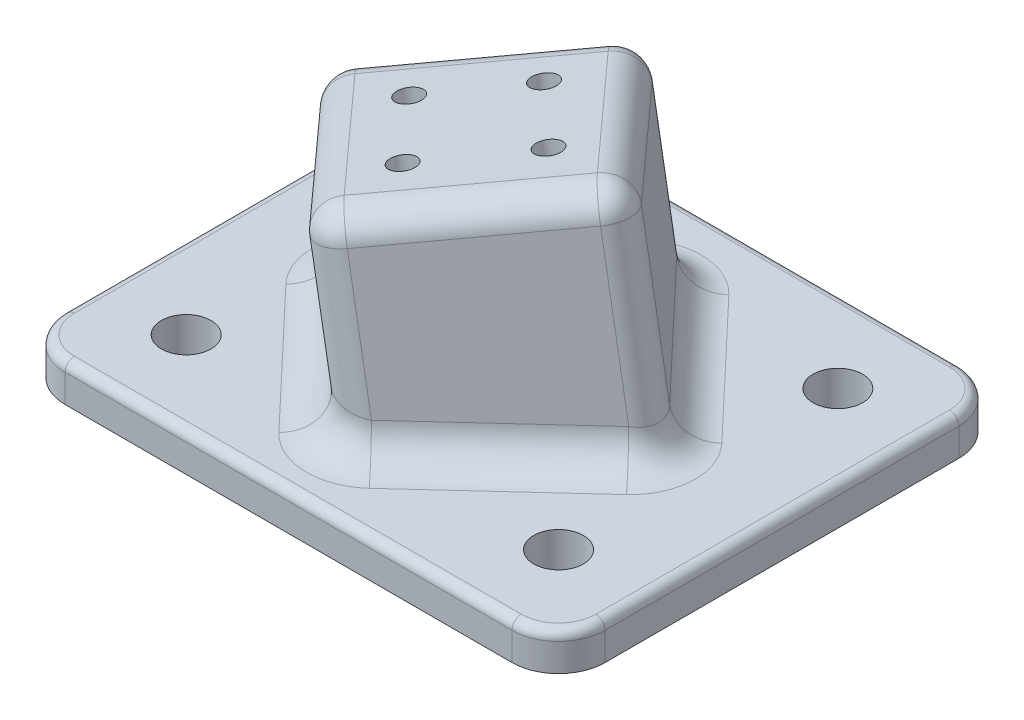
SolidWorks part; units mm, degrees
ref_plane "Front Plane" through (0, 0, 0) normal (0, 0, 1) x (1, 0, 0)
ref_plane "Top Plane" through (0, 0, 0) normal (0, 1, 0) x (1, 0, 0)
ref_plane "Right Plane" through (0, 0, 0) normal (1, 0, 0) x (0, 0, -1)
sketch "Sketch1" plane through (0, 0, 0) normal (0, 1, 0) x (1, 0, 0)
  line L1 (0, 0) -> (63.5, 0)
  line L2 (0, 0) -> (0, -50.8)
  line L3 (0, -50.8) -> (63.5, -50.8)
  line L4 (63.5, 0) -> (63.5, -50.8)
  dimension "D1" = 63.5
  dimension "D2" = 50.8
extrude "Boss-Extrude1" add sketch "Sketch1" along normal blind 5.08
sketch "Sketch2" plane through (0, 5.08, 0) normal (0, 1, 0) x (1, 0, 0)
  line L1 (0, 0) -> (0, -50.8) construction
  line L2 (63.5, 0) -> (0, 0) construction
  point P0 (6.35, -6.35)
  point P1 (57.15, -6.35)
  point P2 (57.15, -44.45)
  point P3 (6.35, -44.45)
  dimension "D1" = 50.8
  dimension "D2" = 38.1
  dimension "D3" = 50.8
  dimension "D4" = 38.1
  dimension "D5" = 6.35
  dimension "D6" = 6.35
ref_plane "Plane2" through (1.9148, -10.8591, 0) normal (-0.1736, 0.9848, 0) x (0, 0, -1)
sketch "Sketch5" plane through (0, 0, 0) normal (0, -1, 0) x (1, 0, 0)
  line L0 (0, 0) -> (0, 50.8) construction
  line L1 (0, 50.8) -> (63.5, 50.8)
  line L2 (0, 50.8) -> (0, 0)
  line L3 (0, 0) -> (63.5, 0)
  line L4 (63.5, 50.8) -> (63.5, 0)
  line L5 (63.5, 0) -> (0, 0) construction
  dimension "D1" = 50.8
  dimension "D2" = 63.5
  dimension "D3" = 0
  dimension "D4" = 0
hole_wizard "1/4 Clearance Hole1" positions "3DSketch2" profile "Sketch8" hole size "1/4" standard "ANSI Inch" end condition up to next
sketch3d "3DSketch2"
  point P0 (6.35, 5.08, 6.35)
  point P3 (6.35, 5.08, 44.45)
  point P6 (57.15, 5.08, 44.45)
  point P9 (57.15, 5.08, 6.35)
sketch "Sketch8" plane through (6.35, 5.08, 6.35) normal (1, 0, 0) x (0, 0, 1)
  line L0 (0, 0) -> (0, 5.08)
  line L1 (0, 5.08) -> (3.3782, 5.08)
  line L2 (3.3782, 5.08) -> (3.3782, 0)
  line L5 (3.3782, 0) -> (0, 0)
  line L11 (0, -6.35) -> (0, 107.95) construction
  dimension "Thru Hole Dia." = 6.7564
  dimension "Thru Hole Depth" = 5.08
sketch "Sketch13" plane through (0, 5.08, 0) normal (0, 1, 0) x (1, 0, 0)
  line L0 (0, 0) -> (63.5, 0)
  line L1 (63.5, 0) -> (63.5, -50.8)
  line L2 (63.5, -50.8) -> (0, -50.8)
  line L3 (0, 0) -> (0, -50.8) construction
  line L4 (0, -50.8) -> (63.5, -50.8) construction
  line L5 (0, -50.8) -> (0, 0)
  line L6 (-5.08, 5.08) -> (68.58, 5.08)
  line L7 (68.58, 5.08) -> (68.58, -55.88)
  line L8 (68.58, -55.88) -> (-5.08, -55.88)
  line L9 (-5.08, -55.88) -> (-5.08, 5.08)
  dimension "D1" = 73.66
  dimension "D2" = 60.96
  dimension "D3" = 5.08
  dimension "D4" = 5.08
extrude "Boss-Extrude3" add sketch "Sketch13" against normal blind 5.08
fillet "Fillet4" radius 1.27 4 edges at (68.58, 5.08, 25.4) (31.75, 5.08, -5.08) (31.75, 5.08, 55.88) (-5.08, 5.08, 25.4)
sketch "Sketch14" plane through (1.9148, -10.8591, 0) normal (-0.1736, 0.9848, 0) x (0, 0, -1)
  line L0 (-25.4, -9.9293) -> (-48.992, -31.9292)
  line L1 (-48.992, -31.9292) -> (-26.9921, -55.5213)
  line L2 (-26.9921, -55.5213) -> (-3.4001, -33.5213)
  line L3 (-3.4001, -33.5213) -> (-25.4, -9.9293)
  line L4 (5.08, 5.0028) -> (-55.88, 5.0028) construction
  line L6 (-55.88, -68.1997) -> (-55.88, 4.3412) construction
  point P6 (-25.4, 5.0028)
  point P11 (-55.88, -31.9292)
  dimension "D1" = 90
  dimension "D2" = 90
  dimension "D3" = 32.258
  dimension "D4" = 32.258
extrude "Boss-Extrude4" add sketch "Sketch14" along normal blind 37.338
sketch "Sketch16" plane through (0, 0, 0) normal (0, -1, 0) x (1, 0, 0)
  line L1 (0, 50.8) -> (63.5, 50.8)
  line L2 (0, 50.8) -> (0, 0)
  line L3 (0, 0) -> (63.5, 0)
  line L4 (63.5, 50.8) -> (63.5, 0)
sketch "Sketch17" plane through (1.9148, -10.8591, 0) normal (0.1736, -0.9848, 0) x (0.9848, 0.1736, 0)
  line L0 (13.5193, 25.5254) -> (33.396, 6.99)
  line L1 (33.396, 6.99) -> (51.9313, 26.8667)
  line L2 (51.9313, 26.8667) -> (32.0546, 45.4021)
  line L3 (32.0546, 45.4021) -> (13.5193, 25.5254)
  line L5 (33.5213, 3.4001) -> (9.9293, 25.4) construction
  line L6 (9.9293, 25.4) -> (31.9292, 48.992) construction
  line L7 (55.5213, 26.9921) -> (31.9292, 48.992) construction
  line L8 (33.5213, 3.4001) -> (55.5213, 26.9921) construction
  dimension "D1" = 2.54
  dimension "D2" = 2.54
  dimension "D3" = 2.54
  dimension "D4" = 2.54
extrude "Cut-Extrude2" cut sketch "Sketch17" against normal blind 32.258
extrude "Cut-Extrude1" cut sketch "Sketch5" along normal up to next contours L2 L3 L4 L1
sketch "Sketch18" plane through (-4.5689, 25.9116, 0) normal (-0.1736, 0.9848, 0) x (0.9848, 0.1736, 0)
  line L0 (33.5213, -3.4001) -> (55.5213, -26.9921) construction
  line L1 (55.5213, -26.9921) -> (31.9292, -48.992) construction
  point P0 (42.3701, -25.8234)
  point P1 (32.7253, -26.196)
  point P2 (23.0733, -25.8288)
  point P3 (32.3273, -16.544)
  point P4 (32.3273, -35.848)
  dimension "D1" = 16.129
  dimension "D2" = 16.129
  dimension "D3" = 9.652
  dimension "D4" = 9.652
  dimension "D5" = 9.652
  dimension "D6" = 9.652
hole_wizard "M3 Clearance Hole1" positions "3DSketch3" profile "Sketch19" hole size "M3" standard "ANSI Metric" end condition through all
sketch3d "3DSketch3"
  point P0 (27.2672, 31.5252, 16.544)
  point P3 (37.1575, 33.2691, 25.8234)
  point P6 (27.2672, 31.5252, 35.848)
  point P9 (18.1538, 29.9182, 25.8288)
sketch "Sketch19" plane through (27.2672, 31.5252, 16.544) normal (0, 0, 1) x (-0.9848, -0.1736, 0)
  line L0 (0, 0) -> (0, 38.2201)
  line L1 (0, 38.2201) -> (1.7, 38.2201)
  line L2 (1.7, 38.2201) -> (1.7, 0)
  line L5 (1.7, 0) -> (0, 0)
  line L11 (0, -6.35) -> (0, 107.95) construction
  dimension "Thru Hole Dia." = 3.4
  dimension "Thru Hole Depth" = 38.2201
fillet "Fillet5" radius 3.81 8 edges at (39.276, 33.6427, 15.1961) (30.7929, 18.4063, 3.4001) (16.8264, 29.6842, 14.4) (7.1982, 16.3579, 25.4) (16.0424, 29.5459, 37.196) (29.2007, 18.268, 48.992) (38.492, 33.5044, 37.9921) (52.7954, 20.3164, 26.9921)
fillet "Fillet6" radius 6.35 8 edges at (68.208, 4.708, -4.708) (-4.708, 4.708, -4.708) (-4.708, 4.708, 55.508) (68.208, 4.708, 55.508) (68.58, 1.905, 55.88) (-5.08, 1.905, 55.88) (-5.08, 1.905, -5.08) (68.58, 1.905, -5.08)
fillet "Fillet7" radius 5.08 8 edges at (44.3124, 5.08, 15.1961) (21.1647, 5.08, 14.4) (20.3564, 5.08, 37.196) (43.504, 5.08, 37.9921) (10.7883, 5.08, 25.4551) (31.582, 5.08, 47.4148) (33.0868, 5.08, 4.9773) (53.8805, 5.08, 26.937)
fillet "Fillet8" radius 1.27 4 edges at (18.754, 24.8657, 35.4637) (37.6682, 28.2008, 36.1344) (38.3287, 28.3173, 16.9284) (19.4145, 24.9822, 16.2577)
